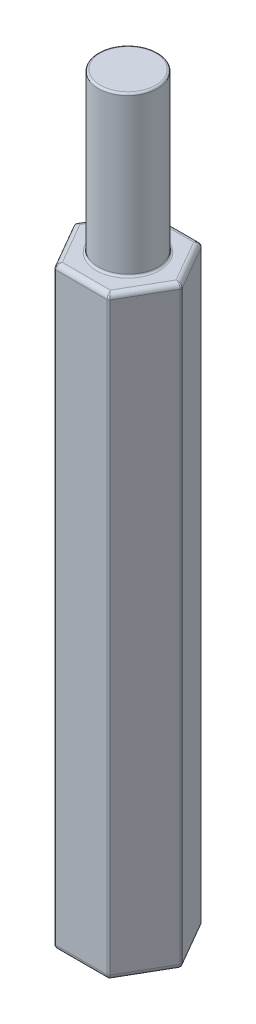
SolidWorks part; units mm, degrees
material "黄铜"
ref_plane "前视基准面" through (0, 0, 0) normal (0, 0, 1) x (1, 0, 0)
ref_plane "上视基准面" through (0, 0, 0) normal (0, 1, 0) x (1, 0, 0)
ref_plane "右视基准面" through (0, 0, 0) normal (1, 0, 0) x (0, 0, -1)
sketch "草图1" plane through (0, 0, 0) normal (0, 1, 0) x (1, 0, 0)
  line L0 (0, 0) -> (5.0665, 0) construction
  line L1 (1.3568, -2.35) -> (2.7135, 0)
  line L2 (2.7135, 0) -> (1.3568, 2.35)
  line L3 (1.3568, 2.35) -> (-1.3568, 2.35)
  line L4 (-1.3568, 2.35) -> (-2.7135, 0)
  line L5 (-2.7135, 0) -> (-1.3568, -2.35)
  line L6 (-1.3568, -2.35) -> (1.3568, -2.35)
  circle A0 centre (0, 0) radius 2.35 construction
  point P1 (0, 0)
  dimension "D1" = 4.7
extrude "凸台-拉伸1" add sketch "草图1" along normal blind 30
sketch "草图3" plane through (0, 0, 0) normal (0, -1, 0) x (1, 0, 0)
  circle A0 centre (0, 0) radius 1.5
  dimension "D1" = 3
extrude "切除-拉伸1" cut sketch "草图3" against normal blind 8
sketch "草图4" plane through (0, 30, 0) normal (0, 1, 0) x (1, 0, 0)
  circle A0 centre (0, 0) radius 1.5
  dimension "D1" = 3
extrude "凸台-拉伸2" add sketch "草图4" along normal blind 8
fillet "圆角5" radius 0.1 6 edges at (-2.7135, 15, 0) (-1.3568, 15, -2.35) (1.3568, 15, -2.35) (2.7135, 15, 0) (1.3568, 15, 2.35) (-1.3568, 15, 2.35)
fillet "圆角6" radius 0.25 12 edges at (1.349, 30, -2.3366) (2.0352, 30, -1.175) (2.6981, 30, 0) (2.0352, 30, 1.175) (1.349, 30, 2.3366) (0, 30, 2.35) (-1.349, 30, 2.3366) (-2.0352, 30, 1.175) (-2.6981, 30, 0) (-2.0352, 30, -1.175) (-1.349, 30, -2.3366) (0, 30, -2.35)
fillet "圆角7" radius 0.1 3 edges at (0, 30, 1.5) (0, 38, 1.5) (0, 0, -1.5)
fillet "圆角8" radius 0.25 12 edges at (-1.349, 0, -2.3366) (0, 0, -2.35) (1.349, 0, -2.3366) (2.0352, 0, -1.175) (2.6981, 0, 0) (2.0352, 0, 1.175) (1.349, 0, 2.3366) (0, 0, 2.35) (-1.349, 0, 2.3366) (-2.0352, 0, 1.175) (-2.6981, 0, 0) (-2.0352, 0, -1.175)
